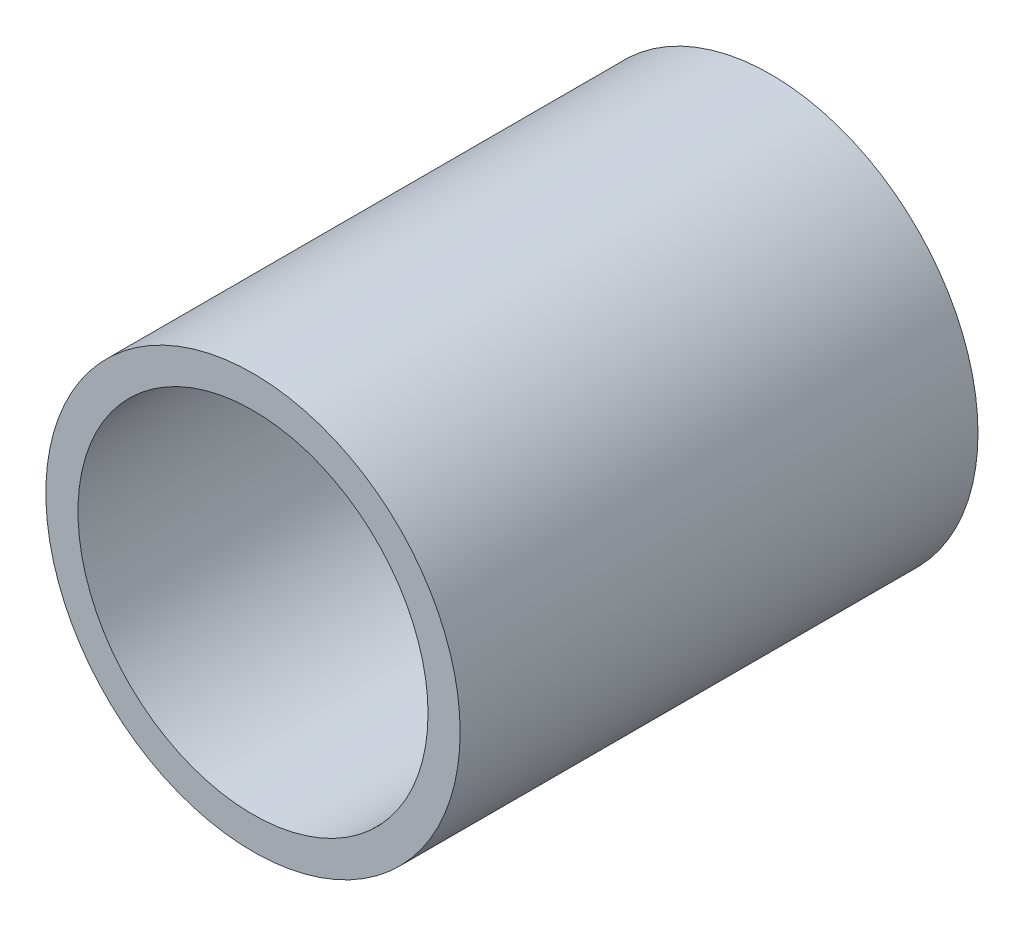
SolidWorks part; units mm, degrees
ref_plane "Front Plane" through (0, 0, 0) normal (0, 0, 1) x (1, 0, 0)
ref_plane "Top Plane" through (0, 0, 0) normal (0, 1, 0) x (1, 0, 0)
ref_plane "Right Plane" through (0, 0, 0) normal (1, 0, 0) x (0, 0, -1)
sketch "Sketch1" plane through (0, 0, 0) normal (0, 0, 1) x (1, 0, 0)
  circle A0 centre (0, 0) radius 25.4
  circle A1 centre (0, 0) radius 21.463
  dimension "D1" = 50.8
  dimension "D2" = 42.926
extrude "Boss-Extrude1" add sketch "Sketch1" along normal blind 63.5
